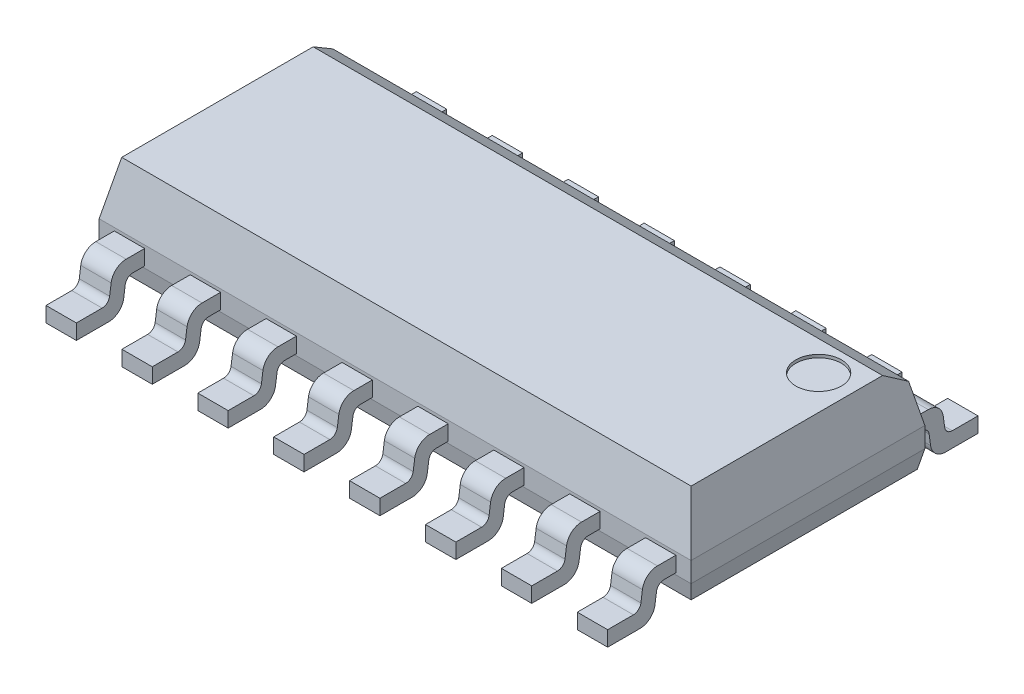
SolidWorks part; units mm, degrees
ref_plane "Front" through (0, 0, 0) normal (0, 0, 1) x (1, 0, 0)
ref_plane "Top" through (0, 0, 0) normal (0, 1, 0) x (1, 0, 0)
ref_plane "Right" through (0, 0, 0) normal (1, 0, 0) x (0, 0, -1)
ref_plane "Pin 1 Plane" through (-0.254, 0, 0) normal (1, 0, 0) x (0, 0, -1)
ref_plane "Body Plane" through (0, 0.1778, 0) normal (0, 1, 0) x (-1, 0, 0)
sketch "Sketch1" plane through (-0.254, 0, 0) normal (1, 0, 0) x (0, 0, -1)
  line L0 (0, 0) -> (-3.0988, 0) construction
  line L1 (0, 0) -> (0, 0.762) construction
  line L2 (2.2654, 0.508) -> (-2.2654, 0.508)
  line L3 (-2.2654, 0.508) -> (-2.3368, 0)
  line L4 (-2.3368, 0) -> (-3.0988, 0)
  line L5 (-3.0988, 0) -> (-3.0988, 0.254)
  line L6 (-3.0988, 0.254) -> (-2.5576, 0.254)
  line L7 (-2.5576, 0.254) -> (-2.4862, 0.762)
  line L8 (-2.4862, 0.762) -> (2.4862, 0.762)
  line L9 (0, 0.762) -> (0, 0.508)
  line L10 (2.2654, 0.508) -> (2.3368, 0)
  line L11 (2.3368, 0) -> (3.0988, 0)
  line L12 (3.0988, 0) -> (3.0988, 0.254)
  line L13 (3.0988, 0.254) -> (2.5576, 0.254)
  line L14 (2.5576, 0.254) -> (2.4862, 0.762)
  dimension "D1" = 98
  dimension "D2" = 0.254
  dimension "D3" = 0.254
  dimension "D4" = 3.0988
  dimension "D5" = 0.762
  dimension "D6" = 0.762
extrude "Pin 1 Leadframe" add sketch "Sketch1" along normal blind 0.508 contours L6 L7 L8 L14 L13 L12 L11 L10 L2 L3 L4 L5
fillet "Outside Radii" radius 0.254 4 edges at (0, 0, -2.3368) (0, 0.762, -2.4862) (0, 0, 2.3368) (0, 0.762, 2.4862)
fillet "Inside Radii" radius 0.127 4 edges at (0, 0.254, -2.5576) (0, 0.508, -2.2654) (0, 0.508, 2.2654) (0, 0.254, 2.5576)
sketch "Sketch2" plane through (0, 0.1778, 0) normal (0, 1, 0) x (1, 0, 0)
  line L0 (0.508, 0) -> (-9.398, 0) construction
  line L1 (-0.936, 0) -> (0.936, 0) construction
  line L2 (0, -1.9558) -> (0, 1.9558) construction
  line L3 (0, -0.936) -> (0, 0.936) construction
  line L5 (0.508, -1.9558) -> (-9.398, -1.9558)
  line L6 (0.508, -1.9558) -> (0.508, 1.9558)
  line L7 (0.508, 1.9558) -> (-9.398, 1.9558)
  line L8 (-9.398, -1.9558) -> (-9.398, 1.9558)
  dimension "D1" = 3.9116
  dimension "D2" = 0.508
  dimension "D3" = 9.906
extrude "Body" add sketch "Sketch2" along normal blind 1.524
pattern_linear "Pins" count 8 spacing 1.27 along (-1, 0, 0) of "Pin 1 Leadframe", "Outside Radii", "Inside Radii"
chamfer "Bottom Chamfer" distance 0.0635 angle 78 4 edges at (-4.445, 0.1778, 1.9558) (-9.398, 0.1778, 0) (-4.445, 0.1778, -1.9558) (0.508, 0.1778, 0) first distance on face at (-4.445, 0.1778, 0)
chamfer "Top Chamfer" distance 0.889 angle 12 4 edges at (0.508, 1.7018, 0) (-4.445, 1.7018, -1.9558) (-4.445, 1.7018, 1.9558) (-9.398, 1.7018, 0) first distance on face at (0.508, 1.0892, 0) first distance on face at (-7.62, 0.635, -1.9558) first distance on face at (-7.62, 0.635, 1.9558) first distance on face at (-9.398, 1.0892, 0)
chamfer "Pin 1 Chamfer" distance 0.254 angle 45 1 edges at (-4.445, 1.7018, -1.7668) first distance on face at (-4.445, 1.2573, -1.8613)
sketch "Sketch3" plane through (0, 1.7018, 0) normal (0, 1, 0) x (1, 0, 0)
  line L0 (-0.254, -0.936) -> (-0.254, 0.936) construction
  line L1 (-9.398, 1.9558) -> (0.508, 1.9558) construction
  circle A0 centre (-0.254, 0.9398) radius 0.381
  dimension "D2" = 0.762
  dimension "D1" = 1.016
extrude "Pin 1 Mark" cut sketch "Sketch3" against normal blind 0.0508
equation "\"D4@Sketch1\" = \"Width\"/2"
equation "\"D1@Sketch2\" = \"Width\"-.090"
equation "\"D3@Sketch2\" =(( (\"Pins\"/2)-1)*.05)+.04"
equation "\"D1@Pins\" = \"Pins\"/2"
